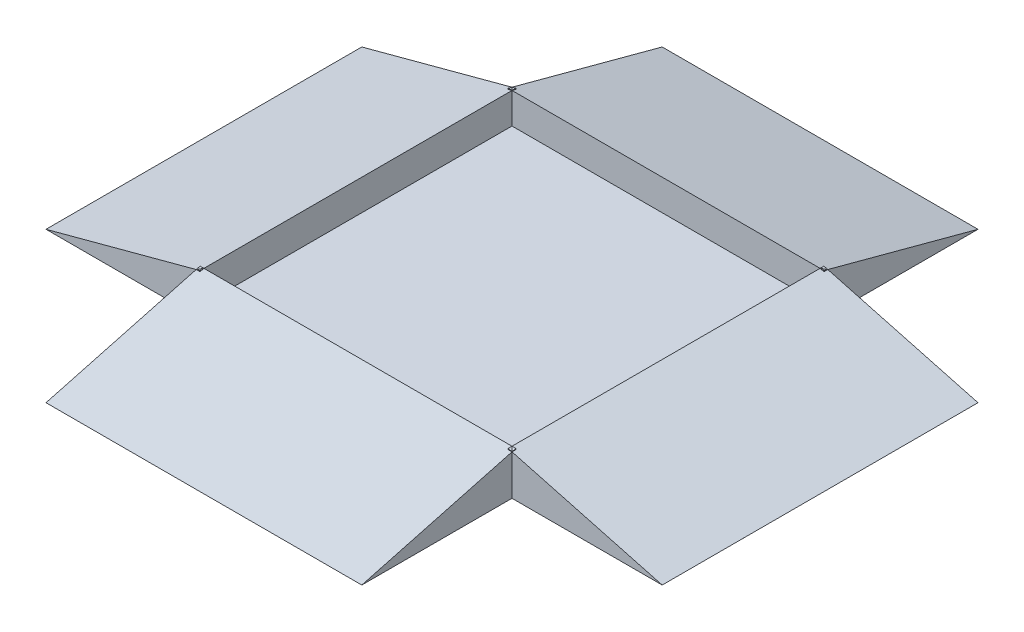
SolidWorks part; units mm, degrees
ref_plane "Front Plane" through (0, 0, 0) normal (0, 0, 1) x (1, 0, 0)
ref_plane "Top Plane" through (0, 0, 0) normal (0, 1, 0) x (1, 0, 0)
ref_plane "Right Plane" through (0, 0, 0) normal (1, 0, 0) x (0, 0, -1)
ref_axis "Axis1" through (0, 28.1347, 0) along (0, -1, 0)
sketch "Sketch1" plane through (0, 0, 0) normal (1, 0, 0) x (0, 0, -1)
  line L0 (0, 0) -> (-200, 0)
  line L1 (-200, 0) -> (0, 53.5898)
  line L2 (0, 53.5898) -> (0, 0)
  line L3 (-100, 0) -> (-100, 26.7949)
  line L4 (-100, 6.7949) -> (0, 6.7949)
  dimension "D1" = 15
  dimension "D2" = 200
  dimension "D3" = 100
  dimension "D4" = 20
extrude "Boss-Extrude1" add sketch "Sketch1" along normal mid plane 205 contours L0 L3 L1 | L4 L3 L0 L2 region at (0, 3.3975, 50) region at (0, 8.9316, 133.3333)
pattern_circular "CirPattern1" count 4 over 360 about axis through (0, 28.1347, 0) along (0, -1, 0) of "Boss-Extrude1"
